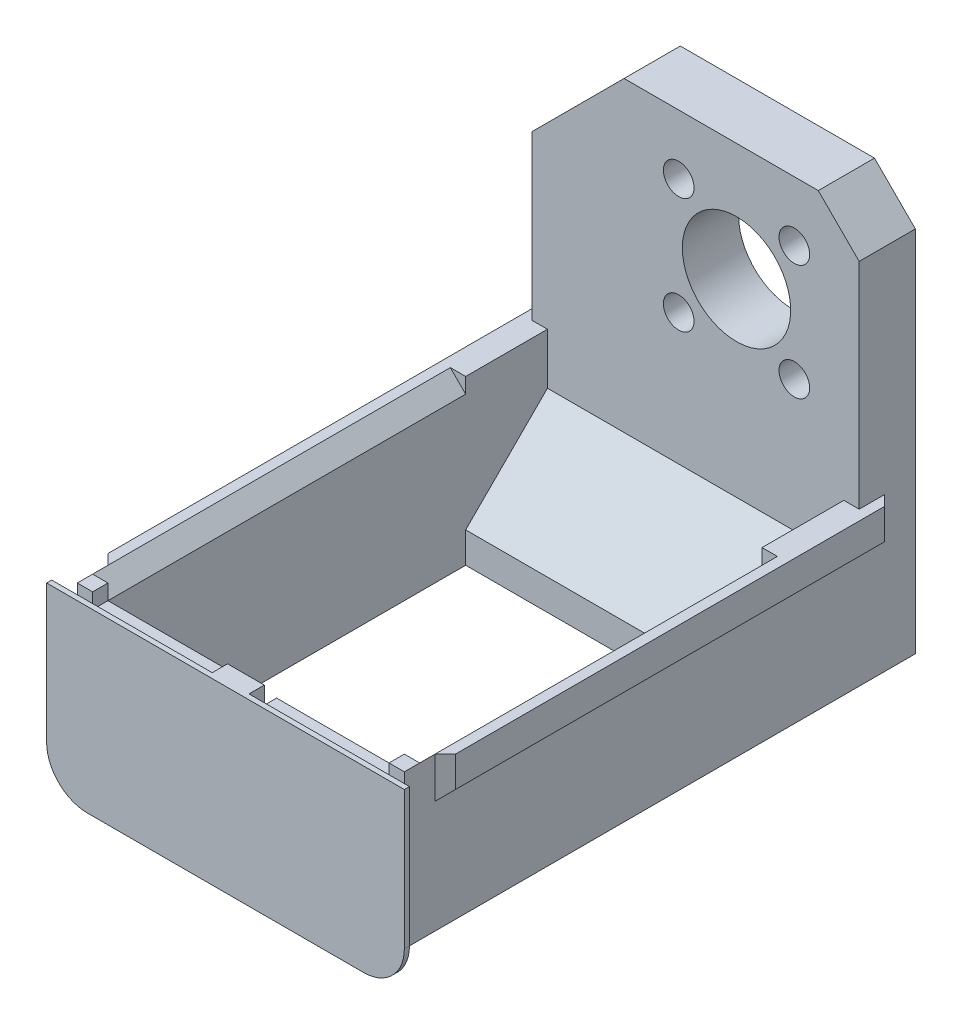
SolidWorks part; units mm, degrees
ref_plane "Płaszczyzna przednia" through (0, 0, 0) normal (0, 0, 1) x (1, 0, 0)
ref_plane "Płaszczyzna górna" through (0, 0, 0) normal (0, 1, 0) x (1, 0, 0)
ref_plane "Płaszczyzna prawa" through (0, 0, 0) normal (1, 0, 0) x (0, 0, -1)
sketch "Szkic1" plane through (0, 0, 0) normal (0, 1, 0) x (1, 0, 0)
  line L1 (-17, 25) -> (17, 25)
  line L2 (-17, 25) -> (-17, -25)
  line L3 (-17, -25) -> (17, -25)
  line L4 (17, 25) -> (17, -25)
  line L5 (-17, 25) -> (17, -25) construction
  line L6 (-17, -25) -> (17, 25) construction
  point P0 (0, 0)
  dimension "D1" = 34
  dimension "D2" = 50
extrude "Dodanie-wyciągnięcie1" add sketch "Szkic1" along normal blind 17
sketch "Szkic3" plane through (0, 17, 0) normal (0, 1, 0) x (1, 0, 0)
  line L0 (17, -25) -> (17, 25) construction
  line L1 (17, 25) -> (-17, 25)
  line L2 (17, 25) -> (17, 19.5)
  line L3 (17, 19.5) -> (-17, 19.5)
  line L4 (-17, 25) -> (-17, 19.5)
  line L5 (17, 25) -> (-17, 25) construction
  line L6 (-17, 25) -> (-17, -25) construction
  line L7 (-17, -25) -> (17, -25) construction
  dimension "D1" = 44.5
extrude "Dodanie-wyciągnięcie2" add sketch "Szkic3" along normal blind 25
sketch "Szkic4" plane through (0, 0, -25) normal (0, 0, -1) x (-1, 0, 0)
  line L1 (-4, 30.5) -> (-9.6569, 36.1569) construction
  line L2 (-4, 30.5) -> (-4, 38.5) construction
  line L3 (-17, 42) -> (17, 42) construction
  line L4 (0, 0) -> (0, 62.7345) construction
  line L6 (-17, 0) -> (17, 0) construction
  circle A0 centre (1.6569, 36.1569) radius 1.5
  circle A1 centre (-4, 30.5) radius 5.3
  circle A2 centre (-4, 30.5) radius 8
  circle A3 centre (-9.6569, 36.1569) radius 1.5
  circle A4 centre (-4, 30.5) radius 8
  circle A5 centre (1.6569, 24.8431) radius 1.5
  circle A6 centre (-4, 30.5) radius 8
  circle A7 centre (-9.6569, 24.8431) radius 1.5
  circle A8 centre (-4, 30.5) radius 8
  point P21 (-4, 30.5)
  dimension "D1" = 4
  dimension "D2" = 11.5
  dimension "D3" = 10.6
  dimension "D4" = 16
  dimension "D5" = 3
  dimension "D6" = 45
  dimension "D7" = 4
extrude "Wytnij-wyciągnięcie2" cut sketch "Szkic4" against normal blind 25 contours A2 A3 | A2 A3 | A2 A0 | A0 A2 | A6 A7 | A6 A7 | A4 A5 | A4 A5 | A1 region at (-2.0886, 36.5886, -25) region at (-1.1893, 35.6893, -25) region at (9.1893, 35.6893, -25) region at (10.0886, 36.5886, -25) region at (-2.0886, 24.4114, -25) region at (-1.1893, 25.3107, -25) region at (9.1893, 25.3107, -25) region at (10.0886, 24.4114, -25) region at (4, 30.5, -25)
chamfer "Sfazowanie1" distance 10 angle 45 1 edges at (-17, 42, -22.25)
chamfer "Sfazowanie2" distance 5 angle 45 1 edges at (17, 42, -22.25)
sketch "Szkic5" plane through (0, 0, 25) normal (0, 0, 1) x (1, 0, 0)
  line L0 (-17, 17) -> (-17, 0) construction
  line L1 (-17, 14) -> (-16, 14)
  line L2 (-17, 14) -> (-17, 0)
  line L3 (-17, 0) -> (-16, 0)
  line L4 (-16, 14) -> (-16, 0)
  line L5 (-17, 0) -> (17, 0) construction
  line L6 (17, 17) -> (17, 0) construction
  line L7 (17, 14) -> (16, 14)
  line L8 (17, 14) -> (17, 0)
  line L9 (17, 0) -> (16, 0)
  line L10 (16, 14) -> (16, 0)
  line L11 (-17, 17) -> (17, 17) construction
  line L12 (-17, 17) -> (-16, 17)
  line L13 (-17, 17) -> (-17, 42)
  line L14 (-17, 42) -> (-16, 42)
  line L15 (-16, 17) -> (-16, 42)
  line L16 (17, 17) -> (16, 17)
  line L17 (17, 17) -> (17, 42)
  line L18 (17, 42) -> (16, 42)
  line L19 (16, 17) -> (16, 42)
  line L20 (-17, 17) -> (17, 17) construction
  line L21 (-7, 42) -> (12, 42) construction
  line L23 (-16, 0) -> (16, 0)
  line L24 (-16, 0) -> (-16, 1)
  line L25 (-16, 1) -> (16, 1)
  line L26 (16, 0) -> (16, 1)
  line M14 (-17, 0) -> (17, 0)
  line M16 (17, 17) -> (-17, 17)
  line M17 (-17, 17) -> (-17, 0)
  dimension "D1" = 1
  dimension "D2" = 3
  dimension "D3" = 1
extrude "Wytnij-wyciągnięcie3" cut sketch "Szkic5" against normal blind 68 contours L25 L4 L10 M14 | L4 L1 M17 M14 | L15 L14 L13 M16 | L9 L8 L7 L10 | L17 L18 L19 L16 region at (-16.5, 7, 25) region at (-16.5, 29.5, 25) region at (0, 0.5, 25)
chamfer "Sfazowanie3" distance 1 angle 45 2 edges at (-16, 14, 0) (16, 14, 0)
chamfer "Sfazowanie4" distance 1 angle 45 2 edges at (-16, 1, 0) (16, 1, 0)
ref_plane "Płaszczyzna1" through (0, 0, 26) normal (0, 0, 1) x (1, 0, 0)
sketch "Szkic7" plane through (0, 0, 26) normal (0, 0, 1) x (1, 0, 0)
  line L0 (0, 17) -> (0, 1) construction
  line L1 (-17, 17) -> (17, 17) construction
  line L2 (-15, 1) -> (15, 1) construction
  line L3 (17, 17) -> (17, 14) construction
  line L4 (17.5, -0.5) -> (-17.5, -0.5)
  line L5 (17.5, -0.5) -> (17.5, 17)
  line L6 (17.5, 17) -> (-17.5, 17)
  line L7 (-17.5, -0.5) -> (-17.5, 17)
  line L8 (17.5, -0.5) -> (-17.5, 17) construction
  line L9 (17.5, 17) -> (-17.5, -0.5) construction
  point P6 (0, 8.25)
  dimension "D1" = 0.5
  dimension "D2" = 1.5
extrude "Dodanie-wyciągnięcie3" add sketch "Szkic7" along normal blind 0.5 separate body
fillet "Zaokrąglenie3" radius 4 2 edges at (17.5, -0.5, 26.25) (-17.5, -0.5, 26.25)
sketch "Szkic8" plane through (0, 17, 0) normal (0, 1, 0) x (1, 0, 0)
  line L0 (-16, 25) -> (-17, 25) construction
  line L1 (-17, 25) -> (-16, 25)
  line L2 (-17, 25) -> (-17, 22)
  line L3 (-17, 22) -> (-16, 22)
  line L4 (-16, 25) -> (-16, 22)
  line L5 (17, 25) -> (16, 25)
  line L6 (17, 25) -> (17, 22)
  line L7 (17, 22) -> (16, 22)
  line L8 (16, 25) -> (16, 22)
  line L9 (-17, -25) -> (-16, -25)
  line L10 (-17, -25) -> (-17, -22)
  line L11 (-17, -22) -> (-16, -22)
  line L12 (-16, -25) -> (-16, -22)
  line L13 (17, -25) -> (16, -25)
  line L14 (17, -25) -> (17, -22)
  line L15 (17, -22) -> (16, -22)
  line L16 (16, -25) -> (16, -22)
  dimension "D1" = 1
  dimension "D2" = 3
extrude "Wytnij-wyciągnięcie4" cut sketch "Szkic8" against normal blind 68
chamfer "Sfazowanie6" distance 1 angle 45 4 edges at (-17, 15.5, -22) (17, 15.5, -22) (17, 15.5, 22) (-17, 15.5, 22)
sketch "Szkic9" plane through (0, 17, 0) normal (0, 1, 0) x (1, 0, 0)
  line L0 (0, -25) -> (0, 25) construction
  line L1 (-16, -25) -> (16, -25) construction
  line L2 (12, 25) -> (-7, 25) construction
  line L3 (-16, -25) -> (-16, -22) construction
  line L4 (14.5, 11.5) -> (-14.5, 11.5)
  line L5 (14.5, 11.5) -> (14.5, -23.5)
  line L6 (14.5, -23.5) -> (-14.5, -23.5)
  line L7 (-14.5, 11.5) -> (-14.5, -23.5)
  line L8 (14.5, 11.5) -> (-14.5, -23.5) construction
  line L9 (14.5, -23.5) -> (-14.5, 11.5) construction
  point P7 (0, -6)
  dimension "D1" = 1.5
  dimension "D2" = 1.5
  dimension "D3" = 35
extrude "Wytnij-wyciągnięcie5" cut sketch "Szkic9" against normal blind 68
chamfer "Sfazowanie7" distance 1.5 angle 45 2 edges at (14.5, 17, 6) (-14.5, 17, 6)
sketch "Szkic10" plane through (0, 0, 25) normal (0, 0, 1) x (1, 0, 0)
  line L0 (-16, 17) -> (16, 17) construction
  line L1 (-2, 21) -> (2, 21)
  line L2 (-2, 21) -> (-2, 13)
  line L3 (-2, 13) -> (2, 13)
  line L4 (2, 21) -> (2, 13)
  line L5 (-2, 21) -> (2, 13) construction
  line L6 (-2, 13) -> (2, 21) construction
  line L7 (-16, 17) -> (-16, 2) construction
  line L8 (-2, 17) -> (-14.5, 17)
  line L9 (-2, 17) -> (-2, 15.5)
  line L10 (-2, 15.5) -> (-14.5, 15.5)
  line L11 (-14.5, 17) -> (-14.5, 15.5)
  line L12 (0, 21) -> (0, 13) construction
  line L13 (14.5, 17) -> (14.5, 15.5)
  line L14 (2, 15.5) -> (14.5, 15.5)
  line L15 (2, 17) -> (2, 15.5)
  line L16 (2, 17) -> (14.5, 17)
  point P0 (0, 17)
  line M5 (16, 17) -> (-16, 17)
  dimension "D1" = 4
  dimension "D2" = 8
  dimension "D3" = 1.5
  dimension "D4" = 1.5
extrude "Wytnij-wyciągnięcie6" cut sketch "Szkic10" against normal blind 10 contours L11 L10 L2 M5 | L4 L14 L13 M5 | L4 L1 L2 M5 | L4 L2 L3 M5 region at (0, 19, 25) region at (0, 15, 25) region at (-8.25, 16.25, 25) region at (8.25, 16.25, 25)
sketch "Szkic11" plane through (0, 0, 26) normal (0, 0, -1) x (-1, 0, 0)
  line L0 (-17.5, 17) -> (17.5, 17) construction
  line L1 (-1.8, 18.8) -> (1.8, 18.8)
  line L2 (-1.8, 18.8) -> (-1.8, 15.2)
  line L3 (-1.8, 15.2) -> (1.8, 15.2)
  line L4 (1.8, 18.8) -> (1.8, 15.2)
  line L5 (-1.8, 18.8) -> (1.8, 15.2) construction
  line L6 (-1.8, 15.2) -> (1.8, 18.8) construction
  line L7 (-1.8, 17) -> (1.8, 17)
  point P0 (0, 17)
  line M10 (17.5, 17) -> (-17.5, 17)
  dimension "D1" = 3.6
  dimension "D2" = 3.6
extrude "Dodanie-wyciągnięcie4" add sketch "Szkic11" along normal blind 1.5 contours L4 L2 L3 M10 region at (0, 16.1, 26)
sketch "Szkic12" plane through (0, 0, -11.5) normal (0, 0, 1) x (1, 0, 0)
  line L0 (16, 17) -> (-16, 17) construction
  line L1 (14.5, 22) -> (-14.5, 22)
  line L2 (14.5, 22) -> (14.5, 12)
  line L3 (14.5, 12) -> (-14.5, 12)
  line L4 (-14.5, 22) -> (-14.5, 12)
  line L5 (14.5, 22) -> (-14.5, 12) construction
  line L6 (14.5, 12) -> (-14.5, 22) construction
  line L7 (-14.5, 1) -> (-14.5, 15.5) construction
  point P0 (0, 17)
  dimension "D1" = 10
extrude "Wytnij-wyciągnięcie7" cut sketch "Szkic12" against normal up to vertex (8 mm away) up to point (16, 17, -19.5)
chamfer "Sfazowanie8" distance 8 angle 45 1 edges at (0, 12, -11.5)
sketch "Szkic13" plane through (0, 0, -25) normal (0, 0, -1) x (-1, 0, 0)
  line L0 (-2, 13) -> (-2, 15.5) construction
  line L1 (2, 15.5) -> (2, 13) construction
  line L2 (-2, 13) -> (-2, 15.5)
  line L3 (2, 15.5) -> (2, 13)
  line L5 (-2, 15.5) -> (2, 15.5)
  line L6 (-2, 15.5) -> (-2, 13)
  line L7 (-2, 13) -> (2, 13)
  line L8 (2, 15.5) -> (2, 13)
extrude "Wytnij-wyciągnięcie8" cut sketch "Szkic13" against normal blind 2 contours L2 L7 L3 L5 region at (0, 14.25, -25)
sketch "Szkic14" plane through (0, 17, 0) normal (0, 1, 0) x (1, 0, 0)
  line L1 (-2, -25) -> (-14.5, -25)
  line L2 (-2, -25) -> (-2, -23.5)
  line L3 (-2, -23.5) -> (-14.5, -23.5)
  line L4 (-14.5, -25) -> (-14.5, -23.5)
  line L5 (2, -25) -> (14.5, -25)
  line L6 (2, -25) -> (2, -23.5)
  line L7 (2, -23.5) -> (14.5, -23.5)
  line L8 (14.5, -25) -> (14.5, -23.5)
